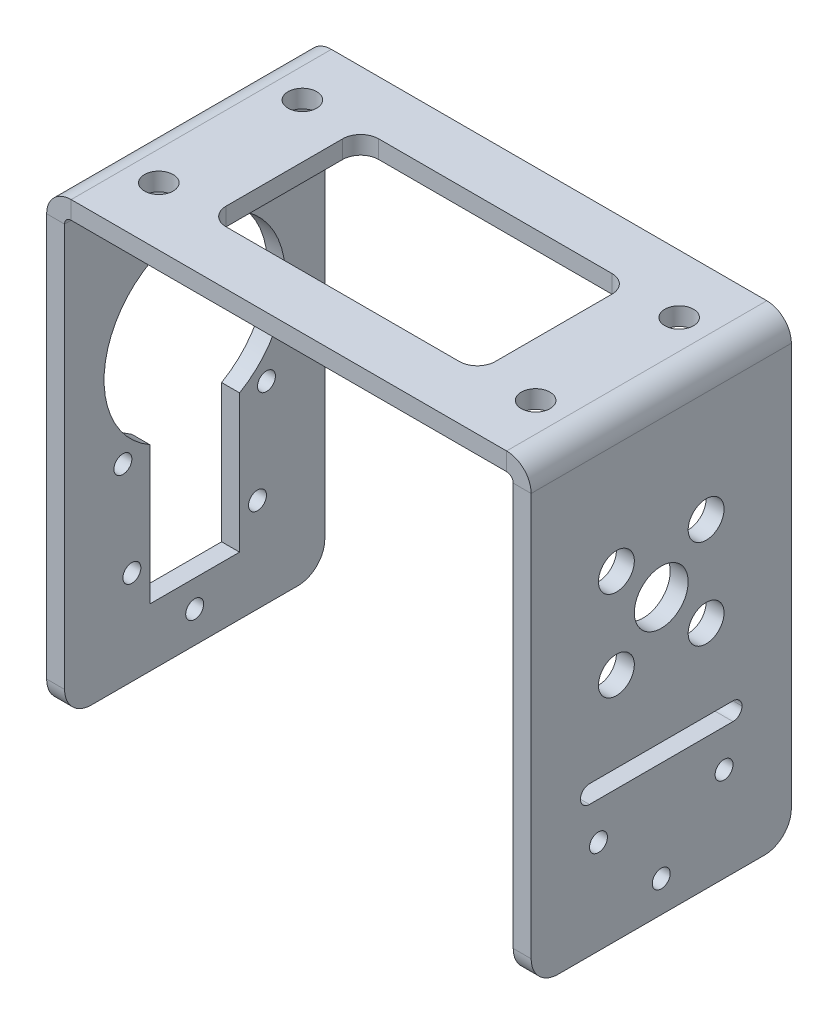
SolidWorks part; units mm, degrees
note: The reader was unsure of these and kept them because the rebuilt part matched: flange length of "边线-法兰1", "边线-法兰2".
ref_plane "前视基准面" through (0, 0, 0) normal (0, 0, 1) x (1, 0, 0)
ref_plane "上视基准面" through (0, 0, 0) normal (0, 1, 0) x (1, 0, 0)
ref_plane "右视基准面" through (0, 0, 0) normal (1, 0, 0) x (0, 0, -1)
sketch "草图1" plane through (0, 0, 0) normal (0, 1, 0) x (1, 0, 0)
  line L1 (25, -14.5) -> (-25, -14.5)
  line L2 (25, -14.5) -> (25, 14.5)
  line L3 (25, 14.5) -> (-25, 14.5)
  line L4 (-25, -14.5) -> (-25, 14.5)
  line L5 (25, -14.5) -> (-25, 14.5) construction
  line L6 (25, 14.5) -> (-25, -14.5) construction
  point P0 (0, 0)
  dimension "D1" = 29
  dimension "D2" = 50
base flange "基体-法兰1" sketch "草图1" thickness 2 reverse thickness direction yes parameters "D1"=0.7366
edge flange "边线-法兰1" sketch "草图8" flange angle 90 flange length 48.65 flange position material outside bend radius 0.7366 thickness 2 relief rectangular parameters "D6"=10
sketch "草图8" plane through (-25, 0, 0) normal (-1, 0, 0) x (0, 0, -1)
  line L2 (-14.5, 0) -> (-14.5, 48.65)
  line L3 (-14.5, 48.65) -> (14.5, 48.65)
  line L4 (14.5, 48.65) -> (14.5, 0)
  line L15 (14.5, 0) -> (-14.5, 0) construction
  line L16 (14.5, 0) -> (-14.5, 0)
bend "边线折弯1" bend radius 0.7366 bend angle 90 parameters "D5"=1
sketch "草图9" plane through (-27, 0, 0) normal (-1, 0, 0) x (0, 0, 1)
  line L0 (-10.0666, 0) -> (9.864, 0) construction
  line L1 (-5, -42.15) -> (-5, -26.7755)
  line L2 (-14.5, -1) -> (14.5, -1) construction
  line L3 (-14.5, -0.7366) -> (-14.5, -48.65) construction
  line L4 (14.5, -48.65) -> (14.5, -0.7366) construction
  line L5 (0, 2) -> (0, -48.65) construction
  line L6 (-14.5, 2) -> (14.5, 2) construction
  line L7 (-14.5, -48.65) -> (14.5, -48.65) construction
  line L8 (5, -42.15) -> (5, -26.7755)
  line L9 (5, -42.15) -> (-5, -42.15)
  arc A0 (5, -26.7755) -> (-5, -26.7755) centre (0, -18) ccw
  circle A1 centre (-8, -27.15) radius 1
  circle A2 centre (-7, -38.15) radius 1
  circle A3 centre (0, -45.15) radius 1
  circle A4 centre (7, -38.15) radius 1
  circle A5 centre (8, -27.15) radius 1
  dimension "D3" = 20.2
  dimension "D9" = 2
  dimension "D10" = 2
  dimension "D11" = 2
  dimension "D1" = 1
  dimension "D2" = 18
  dimension "D4" = 21.5
  dimension "D5" = 10.5
  dimension "D6" = 3.5
  dimension "D7" = 8
  dimension "D8" = 7
  dimension "D12" = 6.5
  dimension "D13" = 10
extrude "切除-拉伸1" cut sketch "草图9" against normal up to next normal cut yes
edge flange "边线-法兰2" sketch "草图12" flange angle 90 flange length 48.65 flange position material outside bend radius 0.7366 thickness 2 relief rectangular parameters "D6"=10
sketch "草图12" plane through (25, 0, 0) normal (1, 0, 0) x (0, 0, 1)
  line L0 (14.5, 0) -> (-14.5, 0) construction
  line L1 (14.5, 0) -> (-14.5, 0)
  line L2 (-14.5, 0) -> (-14.5, 48.65)
  line L3 (-14.5, 48.65) -> (14.5, 48.65)
  line L4 (14.5, 48.65) -> (14.5, 0)
bend "边线折弯2" bend radius 0.7366 bend angle 90 parameters "D5"=2
sketch "草图13" plane through (27, 0, 0) normal (1, 0, 0) x (0, 0, -1)
  line L0 (-10.0316, 0) -> (10.0018, 0) construction
  line L1 (-14.5, -48.65) -> (14.5, -48.65) construction
  line L2 (0, 2) -> (0, -48.65) construction
  line L3 (-14.5, 2) -> (14.5, 2) construction
  line L4 (-14.5, -18) -> (14.5, -18) construction
  line L5 (-14.5, -0.7366) -> (-14.5, -48.65) construction
  line L6 (14.5, -48.65) -> (14.5, -0.7366) construction
  line L7 (9, -34) -> (-9, -34)
  line L14 (-9, -32) -> (-9, -34)
  line L15 (9, -32) -> (-9, -32)
  line L16 (9, -32) -> (9, -34)
  circle A0 centre (0, -18) radius 3
  circle A1 centre (-5, -13) radius 2
  circle A2 centre (5, -13) radius 2
  circle A3 centre (5, -23) radius 2
  circle A4 centre (-5, -23) radius 2
  circle A5 centre (0, -45.15) radius 1
  circle A6 centre (-7, -38.15) radius 1
  circle A7 centre (7, -38.15) radius 1
  point P31 (0, -3)
  dimension "D1" = 6
  dimension "D5" = 4
  dimension "D8" = 2
  dimension "D10" = 2
  dimension "D2" = 18
  dimension "D3" = 5
  dimension "D4" = 5
  dimension "D9" = 3.5
  dimension "D11" = 10.5
  dimension "D12" = 7
  dimension "D13" = 15
  dimension "D6" = 2
  dimension "D7" = 2
extrude "切除-拉伸2" cut sketch "草图13" against normal up to next normal cut yes
fillet "圆角1" radius 3 4 edges at (26, -48.65, -14.5) (26, -48.65, 14.5) (-26, -48.65, -14.5) (-26, -48.65, 14.5)
sketch "草图14" plane through (0, 2, 0) normal (0, 1, 0) x (1, 0, 0)
  line L0 (-27, 0) -> (27, 0) construction
  line L1 (15, -8.5) -> (-15, -8.5)
  line L2 (15, -8.5) -> (15, 8.5)
  line L3 (15, 8.5) -> (-15, 8.5)
  line L4 (-15, -8.5) -> (-15, 8.5)
  line L5 (15, -8.5) -> (-15, 8.5) construction
  line L6 (15, 8.5) -> (-15, -8.5) construction
  line L7 (-27, 14.5) -> (-27, -14.5) construction
  line L8 (27, -14.5) -> (27, 14.5) construction
  line L13 (0, 14.5) -> (0, -14.5) construction
  line L14 (24.2634, 14.5) -> (-24.2634, 14.5) construction
  line L15 (-24.2634, -14.5) -> (24.2634, -14.5) construction
  circle A0 centre (-21, 8) radius 1.6
  circle A1 centre (-21, -8) radius 1.6
  circle A2 centre (21, -8) radius 1.6
  circle A3 centre (21, 8) radius 1.6
  point P0 (0, 0)
  point P5 (0, 0)
  dimension "D4" = 3.2
  dimension "D1" = 17
  dimension "D2" = 30
  dimension "D5" = 8
  dimension "D6" = 21
extrude "切除-拉伸3" cut sketch "草图14" against normal up to next normal cut yes
fillet "圆角2" radius 2 4 edges at (15, 1, -8.5) (15, 1, 8.5) (-15, 1, 8.5) (-15, 1, -8.5)
sketch "草图15" plane through (0, 0, 0) normal (0, 0, 1) x (1, 0, 0)
  line L0 (-25, -7) -> (-18, 0)
  line L3 (-27, -45.65) -> (-27, -0.7366) construction
  line L4 (-24.2634, 2) -> (24.2634, 2) construction
  line L5 (-25, -39.15) -> (-25, -37.15) construction
  line L6 (19.4, 0) -> (22.6, 0) construction
  line L7 (-24.2634, 0) -> (-18, 0)
  line L8 (-25, -0.7366) -> (-25, -7)
  arc A0 (-24.2634, 0) -> (-25, -0.7366) centre (-24.2634, -0.7366) ccw construction
  arc A1 (-24.2634, 0) -> (-25, -0.7366) centre (-24.2634, -0.7366) ccw
  dimension "D1" = 9
  dimension "D2" = 9
extrude "凸台-拉伸1" add sketch "草图15" along normal blind 5 and the other way blind 5
fillet "圆角3" radius 1 4 edges at (26, -34, -9) (26, -32, -9) (26, -34, 9) (26, -32, 9)
mirror "镜向1" about plane through (0, 0, 0) normal (1, 0, 0) of "凸台-拉伸1"
sketch "折弯-线1" plane through (0, 0, 0) normal (0, 1, 0) x (1, 0, 0)
sketch "边界框1" plane through (0, 0, 0) normal (0, 1, 0) x (1, 0, 0)
sheet metal parameters "钣金6" thickness 2 parameters "D1"=0.7366
flat pattern "平板型式6" [suppressed]
sketch "折弯-线2" plane through (0, 0, 0) normal (0, 1, 0) x (1, 0, 0)
sketch "边界框2" [suppressed] plane through (0, 0, 0) normal (0, 1, 0) x (1, 0, 0)
sheet metal parameters "钣金7" thickness 2 parameters "D1"=0.7366
flat pattern "平板型式6" [suppressed]
sketch "折弯-线2" plane through (0, 0, 0) normal (0, 1, 0) x (1, 0, 0)
sketch "边界框2" [suppressed] plane through (0, 0, 0) normal (0, 1, 0) x (1, 0, 0)
bend of the flat pattern "展平-<边线折弯1>1"
sheet metal parameters "钣金8" thickness 2 parameters "D1"=0.7366
flat pattern "平板型式6" [suppressed]
sketch "折弯-线2" plane through (0, 0, 0) normal (0, 1, 0) x (1, 0, 0)
sketch "边界框2" [suppressed] plane through (0, 0, 0) normal (0, 1, 0) x (1, 0, 0)
bend of the flat pattern "展平-<边线折弯1>1"
sheet metal parameters "钣金9" thickness 2 parameters "D1"=0.7366
flat pattern "平板型式6" [suppressed]
sketch "折弯-线2" plane through (0, 0, 0) normal (0, 1, 0) x (1, 0, 0)
sketch "边界框2" [suppressed] plane through (0, 0, 0) normal (0, 1, 0) x (1, 0, 0)
bend of the flat pattern "展平-<边线折弯2>1"
bend of the flat pattern "展平-<边线折弯1>1"
sheet metal parameters "钣金10" thickness 2 parameters "D1"=0.7366
flat pattern "平板型式6" [suppressed]
sketch "折弯-线2" plane through (0, 0, 0) normal (0, 1, 0) x (1, 0, 0)
sketch "边界框2" [suppressed] plane through (0, 0, 0) normal (0, 1, 0) x (1, 0, 0)
bend of the flat pattern "展平-<边线折弯2>1"
bend of the flat pattern "展平-<边线折弯1>1"
sheet metal parameters "钣金11" thickness 2 parameters "D1"=0.7366
flat pattern "平板型式6" [suppressed]
sketch "折弯-线2" plane through (0, 0, 0) normal (0, 1, 0) x (1, 0, 0)
sketch "边界框2" [suppressed] plane through (0, 0, 0) normal (0, 1, 0) x (1, 0, 0)
bend of the flat pattern "展平-<边线折弯2>1"
bend of the flat pattern "展平-<边线折弯1>1"
sheet metal parameters "钣金15" thickness 2 parameters "D1"=0.7366
flat pattern "平板型式6" [suppressed]
sketch "折弯-线2" plane through (0, 0, 0) normal (0, 1, 0) x (1, 0, 0)
sketch "边界框2" [suppressed] plane through (0, 0, 0) normal (0, 1, 0) x (1, 0, 0)
bend of the flat pattern "展平-<边线折弯2>1"
bend of the flat pattern "展平-<边线折弯1>1"
sheet metal parameters "钣金16" thickness 2 parameters "D1"=0.7366
flat pattern "平板型式6" [suppressed]
sketch "折弯-线2" plane through (0, 0, 0) normal (0, 1, 0) x (1, 0, 0)
sketch "边界框2" [suppressed] plane through (0, 0, 0) normal (0, 1, 0) x (1, 0, 0)
bend of the flat pattern "展平-<边线折弯2>1"
bend of the flat pattern "展平-<边线折弯1>1"
